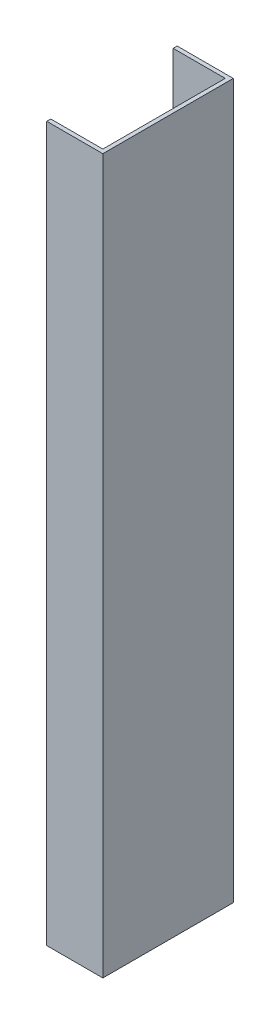
SolidWorks part; units mm, degrees
ref_plane "Alzado" through (0, 0, 0) normal (0, 0, 1) x (1, 0, 0)
ref_plane "Planta" through (0, 0, 0) normal (0, 1, 0) x (1, 0, 0)
ref_plane "Vista lateral" through (0, 0, 0) normal (1, 0, 0) x (0, 0, -1)
sketch "Croquis1" plane through (0, 0, 0) normal (0, 1, 0) x (1, 0, 0)
  line L0 (0, 40.6) -> (0, -40.6)
  line L1 (0, 40.6) -> (-34.925, 40.6)
  line L2 (0, -40.6) -> (-34.925, -40.6)
  line L3 (-34.925, -40.6) -> (-34.925, -38.1)
  line L4 (-34.925, -38.1) -> (-2.5, -38.1)
  line L5 (-2.5, -38.1) -> (-2.5, 38.1)
  line L6 (-2.5, 38.1) -> (-34.925, 38.1)
  line L7 (-34.925, 38.1) -> (-34.925, 40.6)
  point P4 (0, 0)
  dimension "D1" = 2.5
  dimension "D2" = 2.5
  dimension "D3" = 2.5
  dimension "D4" = 76.2
  dimension "D5" = 34.925
  dimension "D6" = 34.925
extrude "Saliente-Extruir1" add sketch "Croquis1" along normal mid plane 444.5
